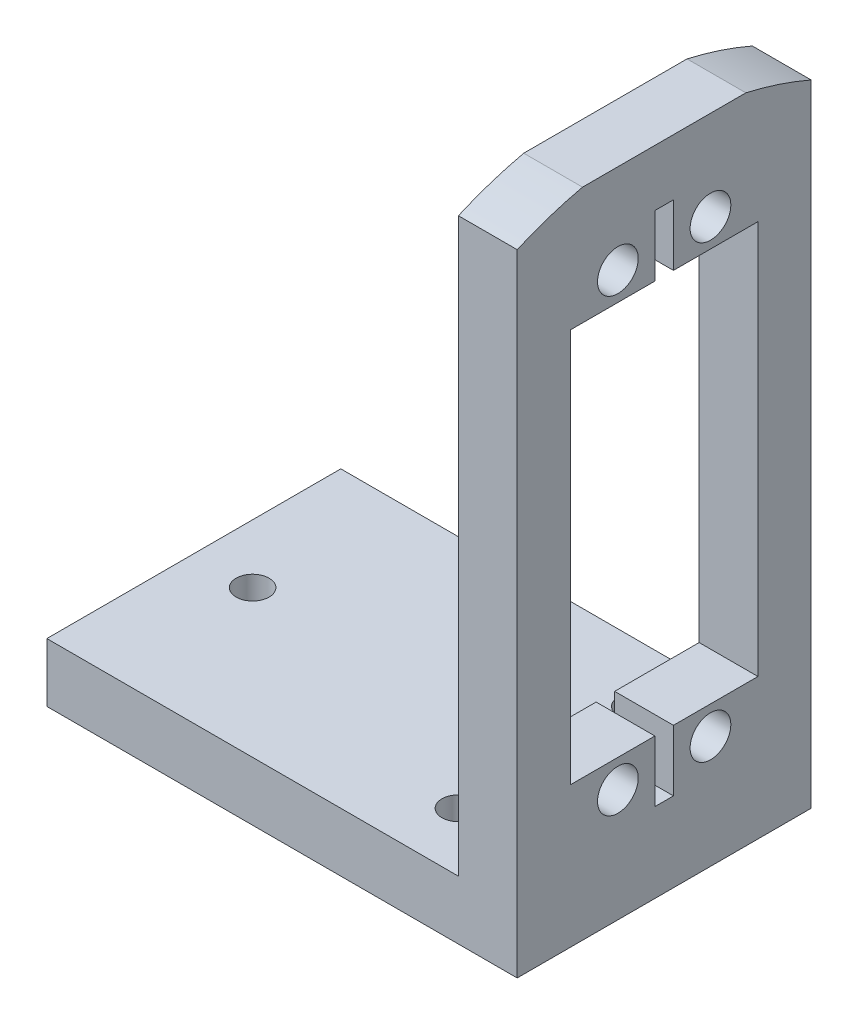
SolidWorks part; units mm, degrees
ref_plane "Front Plane" through (0, 0, 0) normal (0, 0, 1) x (1, 0, 0)
ref_plane "Top Plane" through (0, 0, 0) normal (0, 1, 0) x (1, 0, 0)
ref_plane "Right Plane" through (0, 0, 0) normal (1, 0, 0) x (0, 0, -1)
sketch "Sketch3" plane through (0, 0, 0) normal (1, 0, 0) x (0, 0, -1)
  line L0 (5.748, 51.395) -> (26.002, 8.85) construction
  line L1 (0, 0) -> (31.75, 0)
  line L2 (0, 0) -> (0, 64.095)
  line L3 (0, 64.095) -> (31.75, 64.095)
  line L4 (31.75, 0) -> (31.75, 64.095)
  line L5 (5.748, 51.395) -> (14.875, 51.395)
  line L6 (5.748, 51.395) -> (5.748, 8.85)
  line L7 (5.748, 8.85) -> (14.875, 8.85)
  line L8 (26.002, 51.395) -> (26.002, 8.85)
  line L9 (26.002, 51.395) -> (5.748, 8.85) construction
  line L10 (10.875, 54.4225) -> (20.875, 5.8225) construction
  line L11 (10.875, 5.8225) -> (20.875, 54.4225) construction
  line L12 (16.875, 8.85) -> (26.002, 8.85)
  line L13 (14.875, 8.85) -> (14.875, 2.246)
  line L14 (14.875, 2.246) -> (16.875, 2.246)
  line L15 (16.875, 8.85) -> (16.875, 2.246)
  line L16 (15.875, 30.1225) -> (-939.9401, 30.1225) construction
  line L17 (14.875, 57.999) -> (16.875, 57.999)
  line L18 (14.875, 51.395) -> (14.875, 57.999)
  line L19 (16.875, 51.395) -> (16.875, 57.999)
  line L20 (16.875, 51.395) -> (26.002, 51.395)
  circle A0 centre (10.875, 5.8225) radius 2.2
  circle A1 centre (20.875, 5.8225) radius 2.2
  circle A2 centre (10.875, 54.4225) radius 2.2
  circle A3 centre (20.875, 54.4225) radius 2.2
  point P13 (15.875, 2.246)
  point P22 (15.875, 30.1225)
  point P23 (15.875, 30.1225)
  point P32 (15.875, 20.495)
  point P33 (15.875, 39.75)
  point P34 (15.875, 0)
  point P35 (0, 0)
  point P36 (0, 0)
  point P37 (0, 0)
  dimension "D3" = 4.4
  dimension "D1" = 10
  dimension "D2" = 48.6
  dimension "D4" = 42.545
  dimension "D5" = 20.254
  dimension "D6" = 2
  dimension "D7" = 6.604
  dimension "D12" = 12.7
  dimension "D10" = 31.75
  dimension "D8" = 30.9
  dimension "D9" = 39.75
extrude "Boss-Extrude1" add sketch "Sketch3" along normal blind 6.35
sketch "Sketch5" plane through (6.35, 0, 0) normal (1, 0, 0) x (0, 0, -1)
  line L1 (0, 0) -> (31.75, 0)
  line L2 (0, 0) -> (0, -6.35)
  line L3 (0, -6.35) -> (31.75, -6.35)
  line L4 (31.75, 0) -> (31.75, -6.35)
  dimension "D1" = 6.35
extrude "Boss-Extrude2" add sketch "Sketch5" against normal blind 50.8
sketch "Sketch6" plane through (0, 0, 0) normal (0, 1, 0) x (1, 0, 0)
  line L0 (-44.45, 0) -> (0, 0) construction
  line L2 (-44.45, 31.75) -> (-44.45, 0) construction
  line L3 (0, 15.875) -> (-33.0413, 15.875) construction
  line L5 (0, 31.75) -> (0, 0) construction
  circle A0 centre (-6.35, 6.35) radius 1.777
  circle A2 centre (-38.1, 15.875) radius 1.777
  circle A3 centre (-6.35, 25.4) radius 1.777
  point P14 (0, 0)
  point P15 (0, 0)
  point P20 (0, 0)
  dimension "D1" = 3.554
  dimension "D2" = 6.35
  dimension "D4" = 6.35
  dimension "D3" = 6.35
extrude "Cut-Extrude1" cut sketch "Sketch6" against normal through all
sketch "Sketch7" plane through (6.35, 0, 0) normal (1, 0, 0) x (0, 0, -1)
  line L0 (31.75, 64.095) -> (0, 64.095) construction
  line L1 (0, -6.35) -> (31.75, -6.35) construction
  line L2 (0, 61.7742) -> (0, 82.7489)
  line L3 (0, 64.095) -> (0, -6.35) construction
  line L4 (0, 82.7489) -> (31.75, 82.7489)
  line L5 (31.75, 82.7489) -> (31.75, 61.7742)
  line L6 (31.75, -6.35) -> (31.75, 64.095) construction
  arc A0 (31.75, 61.7742) -> (0, 61.7742) centre (15.875, 25.4) ccw
  point P6 (15.875, 64.095)
  dimension "D2" = 79.375
  dimension "D1" = 31.75
extrude "Cut-Extrude2" cut sketch "Sketch7" against normal through all
equation "\"D1@Sketch6\" = 3.3mm + \"normtol\""
equation "\"tighttol\" = 0.005in"
equation "\"normtol\" = 0.01in"
equation "\"loosetol\" = 0.02in"
equation "\"Fry height\"= 0.5in"
equation "\"Fry spacing\"= 0.5625in"
equation "\"Potato width\"= \"Fry spacing\" * 4"
equation "\"Potato length\"= 80mm"
equation "\"top robot surface separation\" = 1/8+1/8+8mm"
equation "\"D9@Sketch3\"=1+\"top robot surface separation\""
